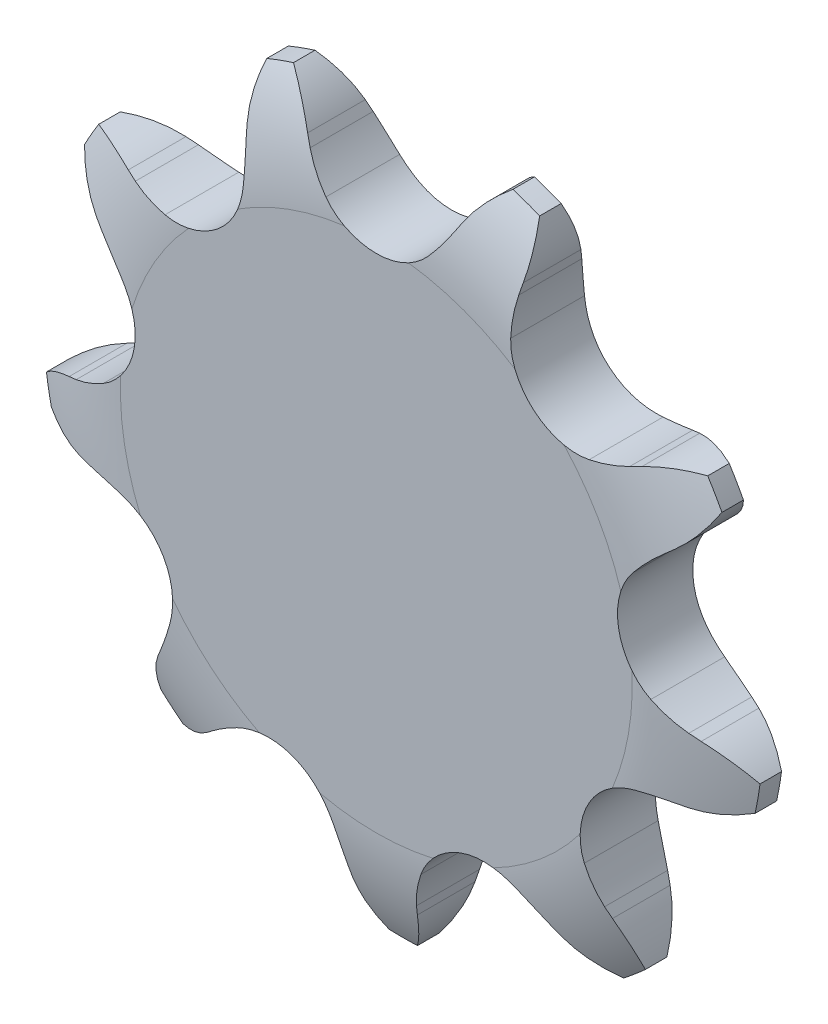
SolidWorks part; units mm, degrees
ref_plane "Front Plane" through (0, 0, 0) normal (0, 0, 1) x (1, 0, 0)
ref_plane "Top Plane" through (0, 0, 0) normal (0, 1, 0) x (1, 0, 0)
ref_plane "Right Plane" through (0, 0, 0) normal (1, 0, 0) x (0, 0, -1)
sketch "Sketch0" plane through (0, 0, 0) normal (0, 0, 1) x (1, 0, 0)
  line L0 (4, -10.9899) -> (0, 0) construction
  line L1 (0, 0) -> (10.1284, -5.8476) construction
  line L2 (0, 0) -> (-4, -10.9899) construction
  line L3 (4, -10.9899) -> (10.1284, -5.8476) construction
  line L4 (4, -10.9899) -> (-4, -10.9899) construction
  line L5 (6.6169, -9.7493) -> (6.322, -9.5008)
  line L6 (4, -10.9899) -> (0, -12.4458) construction
  line L7 (1.1979, -11.7217) -> (1.2641, -11.3417)
  line L8 (0, -10.9899) -> (0, -13.3899) construction
  line L9 (5.2105, -8.7449) -> (2.1016, -14.5107) construction
  line L10 (0, 0) -> (0, -10.9899) construction
  line L11 (6.322, -9.5008) -> (2.1016, -14.5107) construction
  line L12 (0, -13.3899) -> (0, -14.0161) construction
  line L13 (9.3623, -6.4904) -> (6.6169, -9.7493) construction
  circle A0 centre (0, 0) radius 13.3899 construction
  circle A1 centre (0, 0) radius 11.6952 construction
  arc A2 (-4.1222, -15.1007) -> (12.8643, -8.9181) centre (0, 0) ccw
  circle A3 centre (0, 0) radius 14.0161 construction
  circle A4 centre (4, -10.9899) radius 2.5 construction
  arc A7 (5.2105, -8.7449) -> (1.6296, -10.0482) centre (4, -10.9899) ccw
  circle A8 centre (4, -10.9899) radius 2.5506 construction
  arc A9 (6.6169, -9.7493) -> (12.8643, -8.9181) centre (9.3623, -6.4904) ccw
  arc A10 (6.322, -9.5008) -> (5.2105, -8.7449) centre (2.1016, -14.5107) ccw
  arc A11 (1.1979, -11.7217) -> (-4.1222, -15.1007) centre (-3, -10.9899) cw
  arc A12 (1.2641, -11.3417) -> (1.6296, -10.0482) centre (7.7174, -12.4667) cw
  dimension "D1" = 2.5506
  dimension "R" = 2.5506
sketch "Sketch1" plane through (0, 0, 0) normal (1, 0, 0) x (0, 0, -1)
  line L0 (1.4, 0) -> (-1.4, 0)
  line L1 (-1.4, 0) -> (-1.4, 9.5169)
  line L2 (-1.4, 11.6952) -> (0, 11.6952) construction
  line L3 (-0.4, 13.3899) -> (0.4, 13.3899)
  line L5 (1.4, 9.5169) -> (1.4, 0)
  line L7 (0, 13.3899) -> (0, 0) construction
  line L8 (-1.4, 9.5169) -> (1.4, 9.5169) construction
  line L9 (0, 13.3899) -> (0, -13.3899) construction
  line L10 (-1.4, 9.5169) -> (-1.4, 13.3899) construction
  line L11 (-1.4, 13.3899) -> (-0.4, 13.3899) construction
  line L12 (0.4, 13.3899) -> (1.4, 13.3899) construction
  line L13 (1.4, 13.3899) -> (1.4, 9.5169) construction
  line L14 (0, 0) -> (-6.4008, 0) construction
  line L15 (-1.4, 11.6952) -> (-1.4, 6.3952) construction
  line L22 (1.4, 0) -> (-10.6, 0) construction
  line L24 (-1.4, 0) -> (-1.4, 6.3952) construction
  arc A0 (-0.4, 13.3899) -> (-1.4, 9.5169) centre (6.6, 9.5169) ccw
  arc A1 (0.4, 13.3899) -> (1.4, 9.5169) centre (-6.6, 9.5169) cw
  dimension "R" = 8
revolve "Revolve1" add sketch "Sketch1" angle 360 mid plane about L0
extrude "Cut-Extrude1" cut sketch "Sketch0" against normal through all and the other way through all
pattern_circular "CirPattern1" count 9 over 360 about axis through (0, 0, -1.4) along (0, 0, -1) of "Cut-Extrude1"
sketch "Sketch2" plane through (0, 0, 0) normal (0, 0, 1) x (1, 0, 0)
  circle A0 centre (0, 0) radius 3 construction
  circle A1 centre (0, 0) radius 7.5
  circle A2 centre (0, 0) radius 13.39 construction
  dimension "Bore" = 6
  dimension "Hub Dia." = 15
  dimension "OD" = 26.78
extrude "Boss-Extrude1" add sketch "Sketch2" along normal up to vertex (10.6 mm away) from surface up to point (0, 0, 10.6) starting at face at (0, 0, 1.4)
sketch "Sketch3" plane through (0, 0, 0) normal (0, 0, 1) x (1, 0, 0)
  circle A0 centre (0, 0) radius 3 construction
  circle A1 centre (0, 0) radius 3
extrude "Cut-Extrude2" [suppressed] cut sketch "Sketch3" along normal through all and the other way through all
sketch "Sketch4" plane through (0, 0, 0) normal (1, 0, 0) x (0, 0, -1)
  line L0 (-10.6, 7.5) -> (-10.6, 7)
  line L1 (-1.4, 13.3899) -> (-3.5, 13.3899)
  line L2 (-1.4, 13.3899) -> (-1.4, 6.3952)
  line L3 (-1.4, 6.3952) -> (-3.5, 6.3952)
  line L4 (-3.5, 13.3899) -> (-3.5, 6.3952)
  line L9 (-10.6, 7) -> (-10.1, 7.5)
  line L10 (-10.1, 7.5) -> (-10.6, 7.5)
  dimension "C" = 0.5
  dimension "D3" = 2.1
revolve "Cut-Revolve1" cut sketch "Sketch4" angle 360 mid plane about L22
sketch "Sketch5" plane through (0, 0, 0) normal (0, 0, 1) x (1, 0, 0)
  circle A0 centre (0, 0) radius 13.39 construction
  circle A1 centre (0, 0) radius 13.39
extrude "Cut-Extrude3" [suppressed] cut sketch "Sketch5" against normal through all and the other way through all flip side to cut
sketch "Sketch6" plane through (0, 0, 1.4) normal (0, 0, 1) x (1, 0, 0)
  circle A0 centre (0, 0) radius 11
  dimension "D1" = 22
extrude "Cut-Extrude4" cut sketch "Sketch6" along normal blind 10
sketch "Sketch7" plane through (0, 0, 1.4) normal (0, 0, 1) x (1, 0, 0)
  line L0 (0, 9.1446) -> (5.878, 7.0052) construction
  arc A0 (-1.1946, 9.4417) -> (1.1946, 9.4417) centre (0, 11.6952) ccw construction
  arc A1 (5.1539, 8.0006) -> (6.9841, 6.4649) centre (7.5175, 8.9591) ccw construction
  circle A2 centre (0, 0) radius 8.5931 construction
  dimension "D1" = 17.1863
sketch "Sketch9" [suppressed] plane through (0, 0, 1.4) normal (0, 0, 1) x (1, 0, 0)
  line L0 (0, 0) -> (-5.35, 0) construction
  circle A0 centre (0, 0) radius 5.35 construction
  circle A1 centre (-5.35, 0) radius 1.2
  circle A7 centre (-2.675, 4.6332) radius 1.2
  circle A8 centre (2.675, 4.6332) radius 1.2
  circle A9 centre (5.35, 0) radius 1.2
  circle A10 centre (2.675, -4.6332) radius 1.2
  circle A11 centre (-2.675, -4.6332) radius 1.2
  dimension "D1" = 10.7
  dimension "D2" = 2.4
  dimension "D4" = 5.35
  dimension "D5" = 60
  dimension "D3" = 6
extrude "Cut-Extrude5" [suppressed] cut sketch "Sketch9" against normal blind 10
equation "\"360/N@Sketch0\" = 360/\"Teeth@CirPattern1\""
equation "\"Ds@Sketch0\" = 1.005 * \"Dr@Sketch0\" + ( 0.003 * 25.4 ) "
equation "\"R@Sketch0\" = 1/2 * \"Ds@Sketch0\""
equation "\"A@Sketch0\" = 35 +  ( 60 / \"Teeth@CirPattern1\" ) "
equation "\"B@Sketch0\" = 18 -  ( 56 / \"Teeth@CirPattern1\" )"
equation "\"ac@Sketch0\" = 0.8 * \"Dr@Sketch0\""
equation "\"ab@Sketch0\" = 1.4 * \"Dr@Sketch0\""
equation "\"J@Sketch0\" = 0.3 * \"Pitch@Sketch0\""
equation "\"D3@Sketch4\" = \"t@Sketch1\" * 3 / 4"
